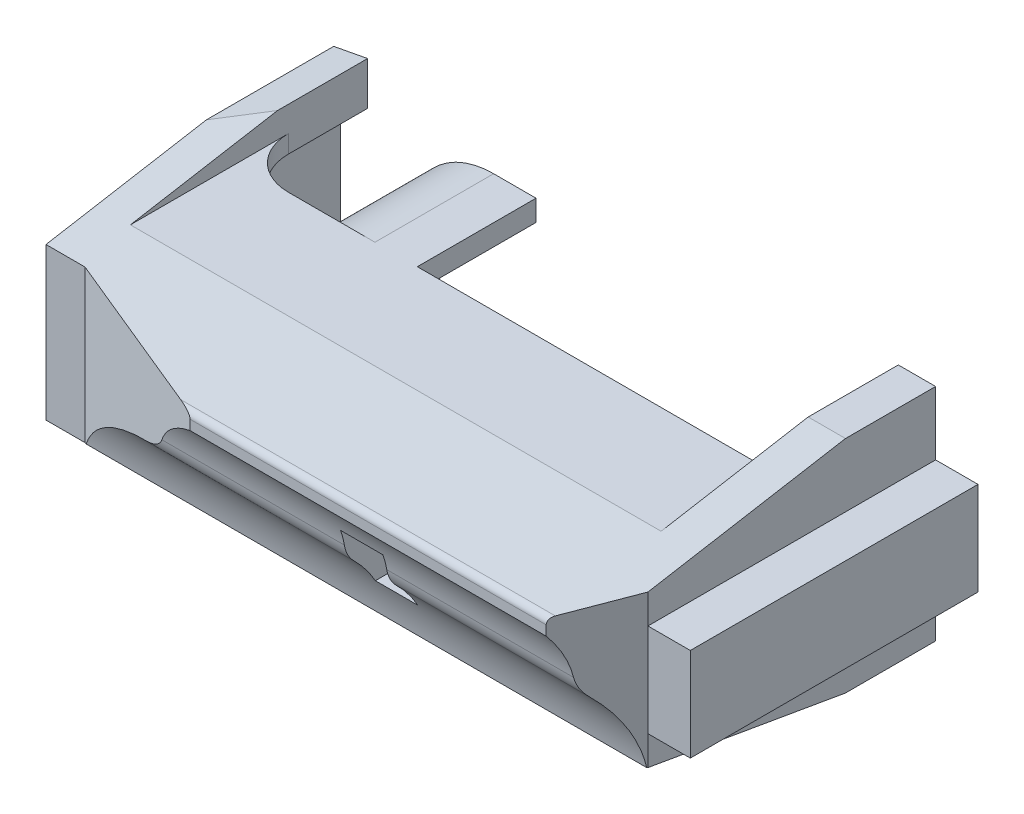
SolidWorks part; units mm, degrees
ref_plane "Front Plane" through (0, 0, 0) normal (0, 0, 1) x (1, 0, 0)
ref_plane "Top Plane" through (0, 0, 0) normal (0, 1, 0) x (1, 0, 0)
ref_plane "Right Plane" through (0, 0, 0) normal (1, 0, 0) x (0, 0, -1)
sketch "Sketch1" plane through (0, 0, 0) normal (0, 0, 1) x (1, 0, 0)
  line L0 (0, 0) -> (57.658, 0) construction
  line L1 (9.398, 6.35) -> (9.398, -6.35)
  line L3 (9.398, 6.35) -> (9.398, 7.7745)
  line L4 (9.398, 7.7745) -> (11.938, 8.255)
  line L5 (11.938, 8.255) -> (11.938, 6.35)
  line L6 (11.938, 6.35) -> (51.689, 6.35)
  line L7 (51.689, 6.35) -> (51.689, 8.255)
  line L8 (51.689, 8.255) -> (54.483, 8.255)
  line L9 (57.658, -3.4925) -> (57.658, 3.4925)
  line L10 (57.658, 3.4925) -> (54.483, 3.4925)
  line L11 (54.483, 3.4925) -> (54.483, 8.255)
  line L12 (54.483, -3.4925) -> (54.483, -8.255)
  line L13 (57.658, -3.4925) -> (54.483, -3.4925)
  line L14 (51.689, -8.255) -> (54.483, -8.255)
  line L15 (51.689, -6.35) -> (51.689, -8.255)
  line L16 (11.938, -6.35) -> (51.689, -6.35)
  line L17 (11.938, -8.255) -> (11.938, -6.35)
  line L18 (9.398, -7.7745) -> (11.938, -8.255)
  line L19 (9.398, -6.35) -> (9.398, -7.7745)
  point P25 (6.604, 0)
  dimension "D1" = 45.085
  dimension "D2" = 16.51
  dimension "D4" = 12.7
  dimension "D5" = 2.54
  dimension "D6" = 2.794
  dimension "D7" = 6.985
  dimension "D8" = 3.175
extrude "Boss-Extrude1" add sketch "Sketch1" against normal blind 34.29
sketch "Sketch2" plane through (9.398, 0, 0) normal (-1, 0, 0) x (0, 0, 1)
  line L0 (-4.699, 8.255) -> (-4.699, 6.35)
  line L1 (-34.29, 8.255) -> (0, 8.255) construction
  line L3 (-4.699, 6.35) -> (0, 6.35)
  line L4 (0, 6.35) -> (0, 8.255)
  line L5 (0, 8.255) -> (-4.699, 8.255)
  line L7 (-34.29, -8.255) -> (0, -8.255) construction
  line L9 (0, 0.889) -> (0, -8.255)
  line L10 (0, -8.255) -> (-4.699, -8.255)
  circle A0 centre (4.4206, -7.1621) radius 9.1849
  circle A1 centre (5.3019, -0.3103) radius 6.6603
  point P4 (5.3019, -0.3103)
  line M17 (0, -7.7745) -> (0, 7.7745)
  line M18 (0, 7.7745) -> (-34.29, 7.7745)
  line M20 (-34.29, -7.7745) -> (0, -7.7745)
  dimension "D3" = 5.461
extrude "Cut-Extrude1" cut sketch "Sketch2" against normal through all contours A1 A0 M17 | A0 A1 L9 | A1 A0 M20 M17 | L0 L3 M17 M18 | L4 L5 L0 M18 | A0 L10 L9 M20 region at (9.398, 8.0147, -2.3495) region at (9.398, 1.6555, -0.5496) region at (9.398, 7.0622, -2.3495) region at (9.398, -4.8862, -2.269) region at (9.398, -1.4136, -0.5478) region at (9.398, -8.0143, -2.3618)
sketch "Sketch3" plane through (0, 0, 0) normal (0, 0, 1) x (1, 0, 0)
  line L1 (35.179, 1.905) -> (38.354, 1.905)
  line L2 (35.179, 1.905) -> (35.179, -2.667)
  line L3 (35.179, -2.667) -> (38.354, -2.667)
  line L4 (38.354, 1.905) -> (38.354, -2.667)
  line L5 (54.483, 6.35) -> (9.398, 6.35) construction
  dimension "D2" = 3.175
  dimension "D3" = 4.572
  dimension "D4" = 4.445
extrude "Cut-Extrude2" cut sketch "Sketch3" against normal blind 9.779
sketch "Sketch4" plane through (0, -8.255, 0) normal (0, -1, 0) x (1, 0, 0)
  line L0 (51.689, -34.29) -> (51.689, -16.51)
  line L1 (11.938, -34.29) -> (51.689, -34.29) construction
  line L2 (51.689, -16.51) -> (40.767, -16.51)
  line L3 (40.767, -16.51) -> (40.767, -19.431)
  line L4 (39.243, -20.955) -> (34.671, -20.955)
  line L5 (33.147, -19.431) -> (33.147, -16.51)
  line L6 (33.147, -16.51) -> (25.4, -16.51)
  line L7 (25.4, -16.51) -> (25.4, -25.4)
  line L8 (25.4, -25.4) -> (15.875, -25.4)
  line L9 (15.875, -25.4) -> (15.875, -16.51)
  line L10 (15.875, -16.51) -> (15.748, -16.51)
  line L11 (11.938, -34.29) -> (11.938, -4.699) construction
  line L12 (11.938, -20.32) -> (11.938, -34.29)
  line L13 (11.938, -34.29) -> (51.689, -34.29)
  line L16 (35.179, -9.779) -> (35.179, -0.9792) construction
  line L17 (35.179, -16.51) -> (38.354, -16.51)
  line L18 (35.179, -16.51) -> (35.179, -18.288)
  line L19 (35.941, -19.05) -> (37.592, -19.05)
  line L20 (38.354, -16.51) -> (38.354, -18.288)
  line L21 (57.658, -34.29) -> (57.658, -3.9994) construction
  line L22 (57.658, -4.699) -> (54.483, -4.699)
  line L24 (54.483, -4.699) -> (51.562, 0)
  line L26 (51.562, 0) -> (57.658, 0)
  line L27 (57.658, 0) -> (57.658, -4.699)
  line L29 (6.604, -4.699) -> (12.319, -4.699)
  line L30 (12.319, -4.699) -> (24.892, 0)
  line L32 (24.892, 0) -> (6.604, 0)
  line L33 (6.604, 0) -> (6.604, -4.699)
  arc A0 (40.767, -19.431) -> (39.243, -20.955) centre (39.243, -19.431) cw
  arc A1 (34.671, -20.955) -> (33.147, -19.431) centre (34.671, -19.431) cw
  arc A2 (37.592, -19.05) -> (38.354, -18.288) centre (37.592, -18.288) ccw
  arc A3 (35.179, -18.288) -> (35.941, -19.05) centre (35.941, -18.288) ccw
  arc A4 (15.748, -16.51) -> (11.938, -20.32) centre (15.748, -20.32) ccw
  point P29 (40.767, -20.955)
  point P32 (33.147, -20.955)
  point P35 (38.354, -19.05)
  point P40 (11.938, -16.51)
  dimension "D11" = 1.524
  dimension "D12" = 0.762
  dimension "D13" = 3.81
  dimension "D2" = 17.78
  dimension "D3" = 10.922
  dimension "D4" = 7.62
  dimension "D5" = 4.445
  dimension "D6" = 26.289
  dimension "D7" = 9.525
  dimension "D8" = 8.89
  dimension "D9" = 3.175
  dimension "D10" = 2.54
  dimension "D14" = 5.969
  dimension "D15" = 6.096
  dimension "D16" = 18.288
  dimension "D17" = 5.715
extrude "Cut-Extrude3" cut sketch "Sketch4" against normal through all
sketch "Sketch5" plane through (0, 0, -34.29) normal (0, 0, -1) x (-1, 0, 0)
  line L0 (-33.147, 6.35) -> (-33.147, -6.35) construction
  line L1 (-22.225, -6.35) -> (-15.875, -6.35)
  line L2 (-22.225, 4.7752) -> (-25.4, 4.7752)
  line L3 (-22.225, -4.7752) -> (-25.4, -4.7752)
  line L4 (-25.4, 4.7752) -> (-25.4, -4.7752)
  line L5 (-40.767, 6.35) -> (-33.147, 6.35)
  line L7 (-9.906, 4.6366) -> (-11.938, 5.021)
  line L8 (-11.938, -8.255) -> (-11.938, 8.255) construction
  line L15 (-9.906, -4.6366) -> (-11.938, -5.021)
  line L16 (-11.938, 5.021) -> (-15.875, 5.021)
  line L17 (-9.906, 4.6366) -> (-9.906, -4.6366)
  line L18 (-57.658, 0) -> (0, 0) construction
  line L21 (-15.875, 6.35) -> (-15.875, -6.35) construction
  line L22 (-22.225, 6.35) -> (-15.875, 6.35)
  line L23 (-15.875, 6.35) -> (-15.875, 5.021)
  line L24 (-15.875, -5.021) -> (-15.875, -6.35)
  line L25 (-11.938, -5.021) -> (-15.875, -5.021)
  line L26 (-22.225, -6.35) -> (-25.4, -6.35) construction
  line L27 (-22.225, 6.35) -> (-25.4, 6.35) construction
  line L28 (-40.767, 6.35) -> (-40.767, 1.5875)
  line L29 (-40.767, 1.5875) -> (-33.147, 1.5875)
  line L30 (-33.147, 6.35) -> (-33.147, 1.5875)
  line L31 (-33.147, -6.35) -> (-33.147, -1.5875)
  line L32 (-40.767, -1.5875) -> (-33.147, -1.5875)
  line L33 (-40.767, -6.35) -> (-40.767, -1.5875)
  line L34 (-40.767, -6.35) -> (-33.147, -6.35)
  line L35 (-55.753, -1.397) -> (-55.753, 1.397)
  line L36 (-55.753, 1.397) -> (-54.182, 1.397)
  line L37 (-54.182, 1.397) -> (-51.689, 5.715)
  line L38 (-51.689, 6.35) -> (-51.689, -6.35) construction
  line L40 (-57.658, -3.4925) -> (-57.658, 3.4925) construction
  line L41 (-54.483, 8.255) -> (-51.689, 8.255) construction
  line L42 (-51.689, 5.715) -> (-51.689, -5.715)
  line L43 (-54.182, -1.397) -> (-51.689, -5.715)
  line L44 (-55.753, -1.397) -> (-54.182, -1.397)
  arc A0 (-22.225, -6.35) -> (-22.225, 6.35) centre (-22.225, 0) ccw construction
  arc A1 (-22.225, 6.35) -> (-22.225, -6.35) centre (-22.225, 0) cw
  arc A2 (-22.225, 4.7752) -> (-22.225, -4.7752) centre (-22.225, 0) cw
  arc A3 (-25.4, 5.4993) -> (-25.4, -5.4993) centre (-22.225, 0) ccw construction
  point P27 (-51.689, 0)
  point P61 (-55.753, 0)
  line M5 (-11.938, 8.255) -> (-11.938, -8.255)
  dimension "D4" = 12.7
  dimension "D5" = 1.5748
  dimension "D6" = 9.525
  dimension "D7" = 9.5504
  dimension "D8" = 4.7625
  dimension "D9" = 2.54
  dimension "D10" = 2.794
  dimension "D11" = 1.905
  dimension "D12" = 30
extrude "Cut-Extrude4" cut sketch "Sketch5" against normal up to surface (17.78 mm away) contours L30 L5 L28 L29 | L33 L34 L31 L32 | A2 L2 L4 L3 | L22 A1 L23 | L24 A1 L1 | L17 L7 L15 M5 | L35 L44 L43 L42 L37 L36 region at (14.9377, 0, -34.29) region at (10.9355, 0, -34.29) region at (21.8553, 0, -34.29) region at (36.957, 3.9687, -34.29) region at (36.957, -3.9687, -34.29) region at (53.1365, 0, -34.29) up to face at (29.2735, 0, -16.51)
sketch "Sketch6" plane through (9.398, 0, 0) normal (-1, 0, 0) x (0, 0, 1)
  line L7 (-26.2464, 9.3507) -> (-37.1615, 9.3507)
  line L8 (-26.2464, 9.3507) -> (-26.2464, -9.3373)
  line L9 (-26.2464, -9.3373) -> (-37.1615, -9.3373)
  line L10 (-37.1615, 9.3507) -> (-37.1615, -9.3373)
  point P2 (0, 0)
extrude "Cut-Extrude5" cut sketch "Sketch6" against normal blind 74.422
sketch "Sketch7" plane through (9.398, 0, 0) normal (-1, 0, 0) x (0, 0, 1)
  line L3 (-19.4945, 8.255) -> (-19.4945, 8.7078)
  line L4 (-19.4945, 8.7078) -> (-4.699, 8.833)
  line L11 (3.1242, 5.3427) -> (3.1242, 8.833)
  line L12 (3.1242, 8.833) -> (-4.699, 8.833)
  line L13 (-19.4945, 8.255) -> (3.1242, 4.3431)
  line L14 (3.1242, 4.3431) -> (3.1242, 5.3427)
  line L15 (3.1242, -4.3431) -> (3.1242, -5.3427)
  line L16 (-19.4945, -8.255) -> (3.1242, -4.3431)
  line L17 (3.1242, -8.833) -> (-4.699, -8.833)
  line L18 (3.1242, -5.3427) -> (3.1242, -8.833)
  line L19 (-19.4945, -8.7078) -> (-4.699, -8.833)
  line L20 (-19.4945, -8.255) -> (-19.4945, -8.7078)
  point P7 (0, 0)
extrude "Cut-Extrude6" cut sketch "Sketch7" against normal blind 74.422
fillet "Fillet2" radius 0.508 1 edges at (38.227, 4.8834, 0)
fillet "Fillet3" radius 2.54 2 edges at (45.3782, -0.0179, -1.352) (28.2268, -0.0179, -1.352)
